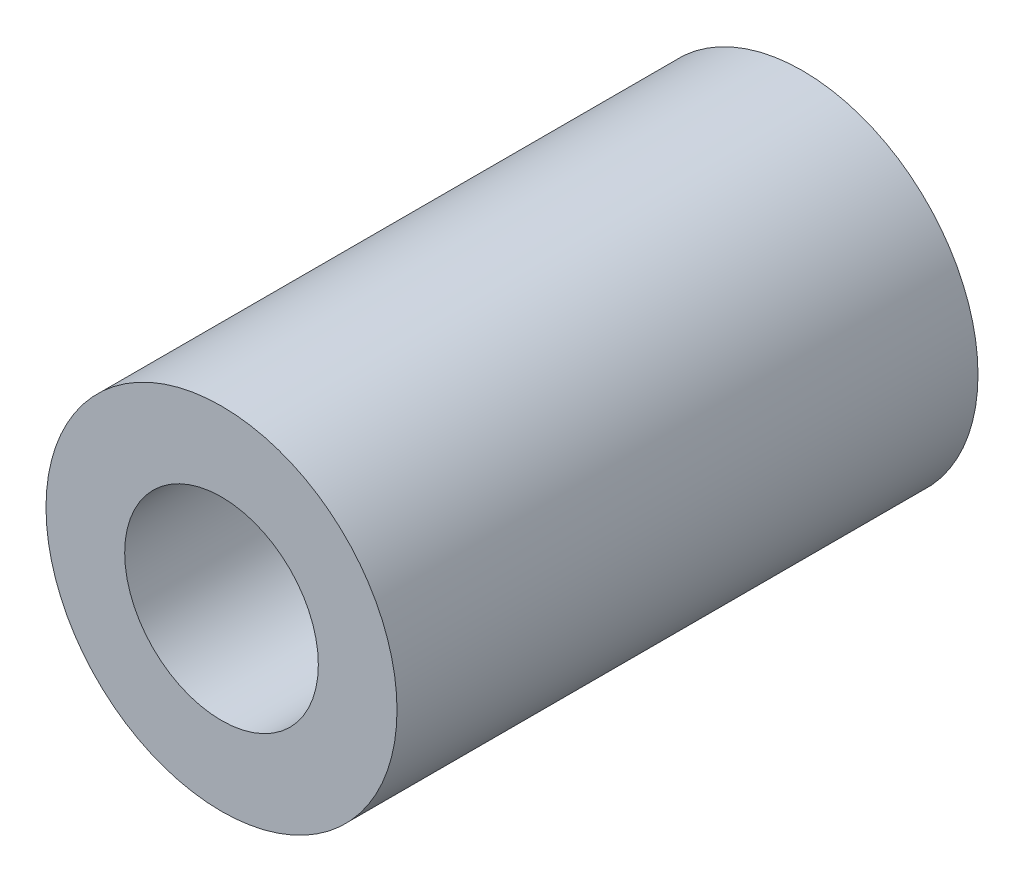
SolidWorks part; units mm, degrees
ref_plane "Front Plane" through (0, 0, 0) normal (0, 0, 1) x (1, 0, 0)
ref_plane "Top Plane" through (0, 0, 0) normal (0, 1, 0) x (1, 0, 0)
ref_plane "Right Plane" through (0, 0, 0) normal (1, 0, 0) x (0, 0, -1)
sketch "Sketch1" plane through (0, 0, 0) normal (0, 0, 1) x (1, 0, 0)
  circle A0 centre (0, 0) radius 11.5094
  dimension "D1" = 23.0188
extrude "Boss-Extrude1" add sketch "Sketch1" along normal blind 38.1
sketch "Sketch2" plane through (0, 0, 38.1) normal (0, 0, 1) x (1, 0, 0)
  circle A0 centre (0, 0) radius 6.35
extrude "Cut-Extrude1" cut sketch "Sketch2" against normal through all both and the other way through all
